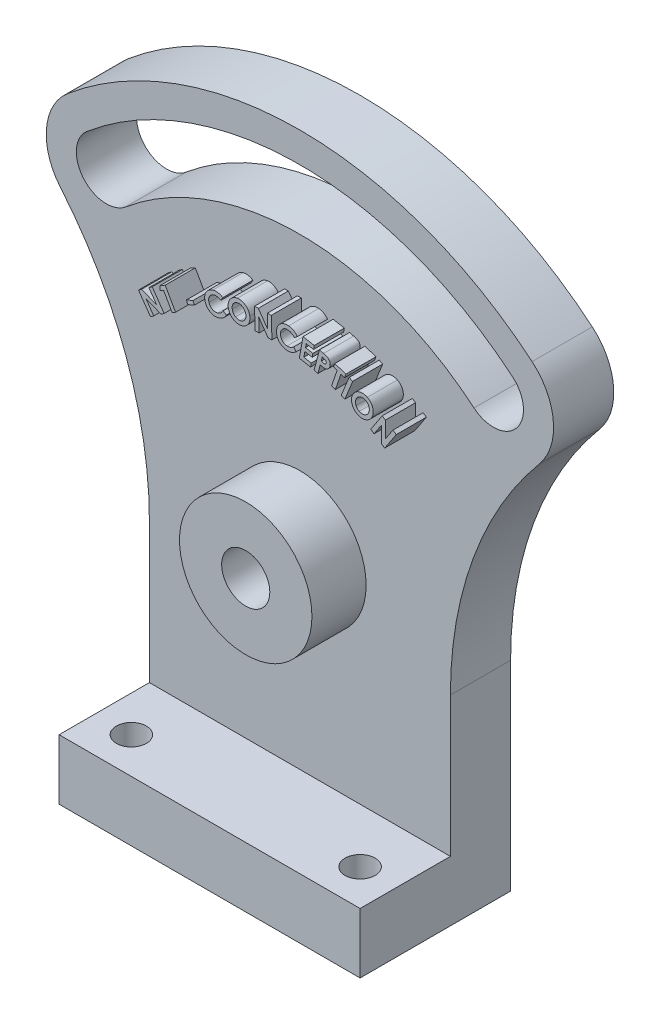
SolidWorks part; units mm, degrees
ref_plane "Front Plane" through (0, 0, 0) normal (0, 0, 1) x (1, 0, 0)
ref_plane "Top Plane" through (0, 0, 0) normal (0, 1, 0) x (1, 0, 0)
ref_plane "Right Plane" through (0, 0, 0) normal (1, 0, 0) x (0, 0, -1)
sketch "Sketch1" plane through (0, 0, 0) normal (0, 0, 1) x (1, 0, 0)
  line L0 (0, 0) -> (15430.6309, 0) construction
  line L1 (0, 0) -> (0, 15430.6309) construction
  line L2 (-25, 10) -> (25, 10)
  line L3 (-25, 0) -> (25, 0)
  line L4 (-25, 0) -> (-25, 33.2122)
  line L6 (25, 0) -> (25, 33.2122)
  circle A0 centre (0, 42) radius 11
  circle A1 centre (0, 42) radius 4
  arc A2 (32.1394, 80.3022) -> (-32.1394, 80.3022) centre (0, 42) ccw construction
  arc A3 (38.5673, 87.9627) -> (-38.5673, 87.9627) centre (0, 42) ccw
  arc A4 (25.7115, 72.6418) -> (-25.7115, 72.6418) centre (0, 42) ccw
  arc A5 (25.7115, 72.6418) -> (38.5673, 87.9627) centre (32.1394, 80.3022) ccw
  arc A6 (-38.5673, 87.9627) -> (-25.7115, 72.6418) centre (-32.1394, 80.3022) ccw
  arc A7 (32.1394, 80.3022) -> (-32.1394, 80.3022) centre (0, 42) ccw construction
  arc A8 (35.3533, 84.1324) -> (-35.3533, 84.1324) centre (0, 42) ccw
  arc A9 (28.9254, 76.472) -> (-28.9254, 76.472) centre (0, 42) ccw
  arc A10 (28.9254, 76.472) -> (35.3533, 84.1324) centre (32.1394, 80.3022) ccw
  arc A11 (-35.3533, 84.1324) -> (-28.9254, 76.472) centre (-32.1394, 80.3022) ccw
  arc A12 (25, 33.2122) -> (39.7998, 73.8743) centre (88.2591, 33.2122) cw
  arc A13 (-25, 33.2122) -> (-39.7998, 73.8743) centre (-88.2591, 33.2122) ccw
  point P16 (0, 92)
  point P21 (0, 92)
  point P29 (0, 0)
  point P30 (0, 0)
  point P35 (0, 0)
  point P36 (-62.9917, 43.708)
  point P37 (0, 0)
  point P38 (0, 92)
  point P39 (0, 0)
  dimension "D4" = 8
  dimension "D5" = 22
  dimension "D6" = 50
  dimension "D7" = 10
  dimension "D8" = 5
  dimension "D1" = 50
  dimension "D2" = 42
  dimension "D3" = 10
  dimension "D9" = 80
extrude "Boss-Extrude2" add sketch "Sketch1" along normal blind 25 contours L3 L6 L2 L4 region at (0, 5, 0)
extrude "Boss-Extrude4" add sketch "Sketch1<6>" along normal blind 10 contours A13 L4 L2 L6 A12 A5 A4 A6 A0 | A3 A6 A4 A5 A11 A8 A10 A9 region at (-23.9267, 21.6061, 0) region at (0, 86.0847, 0)
sketch "Sketch1<6>" plane through (0, 0, 0) normal (0, 0, 1) x (1, 0, 0) same geometry as "Sketch1"
extrude "Boss-Extrude5" add sketch "Sketch1<7>" along normal blind 19 contours A0 A1 region at (-10.6889, 42, 0)
sketch "Sketch1<7>" plane through (0, 0, 0) normal (0, 0, 1) x (1, 0, 0) same geometry as "Sketch1"
hole_wizard "Ø5.0mm Dowel Hole1" positions "Sketch2" profile "Sketch3" hole size "Ø5.0" standard "ISO" end condition up to next
sketch "Sketch2" plane through (0, 10, 0) normal (0, 1, 0) x (1, 0, 0)
  line L0 (-25, -25) -> (-25, 0) construction
  line L2 (-25, -25) -> (25, -25) construction
  line L3 (25, -25) -> (25, 0) construction
  point P0 (-19, -19)
  point P2 (19, -19)
  point P7 (0, 0)
  point P14 (-21.8981, -25)
  dimension "D1" = 6
  dimension "D2" = 6
  dimension "D3" = 6
sketch "Sketch3" plane through (-19, 10, 19) normal (1, 0, 0) x (0, 0, 1)
  line L0 (0, 0) -> (0, 10)
  line L1 (0, 10) -> (2.5, 10)
  line L2 (2.5, 10) -> (2.5, 0)
  line L5 (2.5, 0) -> (0, 0)
  line L11 (0, -6.35) -> (0, 107.95) construction
  dimension "Thru Hole Dia." = 5
  dimension "Thru Hole Depth" = 10
sketch "Sketch4" plane through (0, 0, 0) normal (0, 0, 1) x (1, 0, 0)
  text T0 "<b>                                                                           N1 - CONCEPTION</b>"
extrude "Boss-Extrude8" add sketch "Sketch4" along normal blind 15
